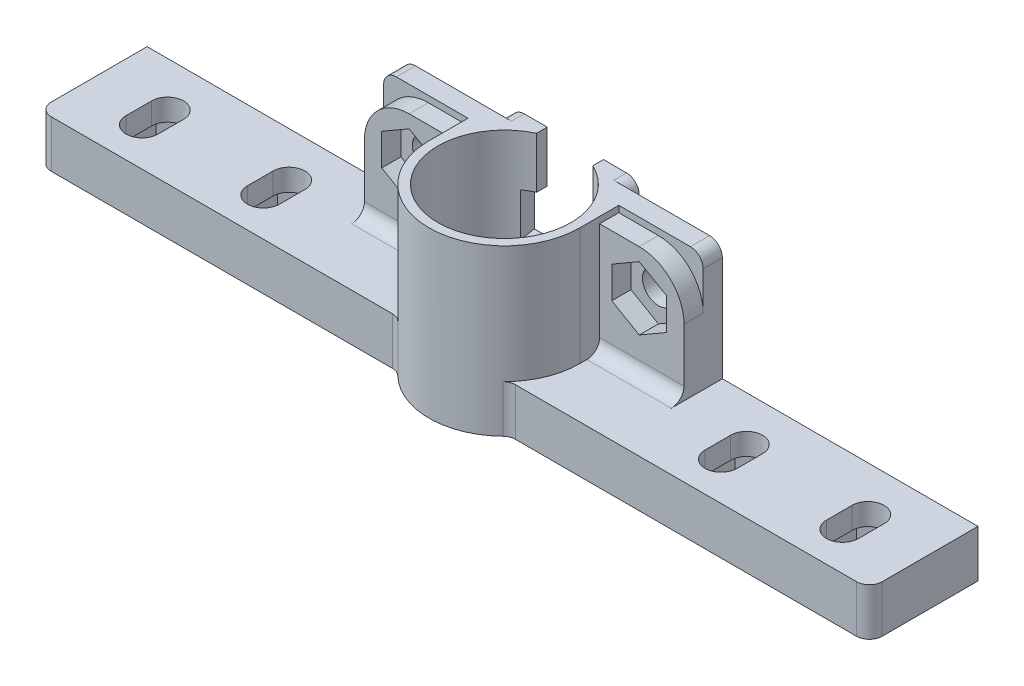
SolidWorks part; units mm, degrees
note: '?' marks a value the reader was unsure of.
ref_plane "Front Plane" through (0, 0, 0) normal (0, 0, 1) x (1, 0, 0)
ref_plane "Top Plane" through (0, 0, 0) normal (0, 1, 0) x (1, 0, 0)
ref_plane "Right Plane" through (0, 0, 0) normal (1, 0, 0) x (0, 0, -1)
sketch "Sketch1" plane through (0, 0, 0) normal (0, 1, 0) x (1, 0, 0)
  line L0 (-2.0019, 5.55) -> (2.0019, 5.55)
  line L1 (5, 4.55) -> (12.5, 4.55)
  line L2 (5.0505, 3.05) -> (12.5, 3.05)
  line L3 (12.5, 4.55) -> (12.5, 3.05)
  line L4 (0, 13.9078) -> (0, -10.692) construction
  line L5 (2.0019, 5.55) -> (5, 5.55)
  line L6 (5, 5.55) -> (5, 4.55)
  line L7 (-5.0505, 3.05) -> (-12.5, 3.05)
  line L8 (-12.5, 4.55) -> (-12.5, 3.05)
  line L9 (-5, 4.55) -> (-12.5, 4.55)
  line L10 (-5, 5.55) -> (-5, 4.55)
  line L11 (-2.0019, 5.55) -> (-5, 5.55)
  line L12 (-5.9, 0) -> (-5.9, 3.05)
  line L13 (5.9, 0) -> (5.9, 3.05)
  circle A0 centre (0, 0) radius 5.2
  circle A1 centre (0, 0) radius 5.9
  point P6 (0, 5.2)
  dimension "D1" = 10.4
  dimension "D2" = 0.7
  dimension "D3" = 0.35
  dimension "D4" = 1
  dimension "D5" = 1.5
  dimension "D6" = 25
  dimension "D7" = 10
extrude "Base shape" add sketch "Sketch1" along normal blind 11.4 contours A1 L9 L8 L7 | A1 L11 L10 | L4 L0 A1 A0 | L0 L4 A0 A1 | A1 L6 L5 | A1 L2 L3 L1
sketch "Sketch2" plane through (0, 0, 0) normal (0, -1, 0) x (1, 0, 0)
  line L9 (-5.9, -3.05) -> (-12.5, -3.05)
  line L10 (-12.5, -3.05) -> (-12.5, -4.55)
  line L11 (-12.5, -4.55) -> (-5, -4.55)
  line L12 (-5, -4.55) -> (-5, -5.55)
  line L13 (-5, -5.55) -> (5, -5.55)
  line L14 (5, -5.55) -> (5, -4.55)
  line L15 (5, -4.55) -> (12.5, -4.55)
  line L16 (12.5, -4.55) -> (12.5, -3.05)
  line L17 (12.5, -3.05) -> (5.9, -3.05)
  line L18 (-5.9, -3.05) -> (-12.5, -3.05)
  line L19 (-12.5, -3.05) -> (-12.5, -4.55)
  line L20 (-12.5, -4.55) -> (-5, -4.55)
  line L21 (-5, -4.55) -> (-5, -5.55)
  line L22 (-5, -5.55) -> (5, -5.55)
  line L23 (5, -5.55) -> (5, -4.55)
  line L24 (5, -4.55) -> (12.5, -4.55)
  line L25 (12.5, -4.55) -> (12.5, -3.05)
  line L26 (12.5, -3.05) -> (5.9, -3.05)
  line L29 (5.9, -3.05) -> (5.9, 0)
  line L30 (5.9, -3.05) -> (5.9, 0)
  line L31 (-5.9, 0) -> (-5.9, -3.05)
  line L32 (-5.9, 0) -> (-5.9, -3.05)
  arc A1 (5.9, 0) -> (-5.9, 0) centre (0, 0) ccw
  arc A2 (5.9, 0) -> (-5.9, 0) centre (0, 0) ccw
  dimension "D1" = 0
extrude "Bottom extrude" add sketch "Sketch2" along normal blind 1.5
sketch "Sketch3" plane through (0, 0, 0) normal (0, 1, 0) x (1, 0, 0)
  circle A0 centre (0, 0) radius 3
  dimension "D1" = 6
extrude "Pin cut" cut sketch "Sketch3" against normal up to next
sketch "Sketch5" plane through (0, 0, -4.55) normal (0, 0, -1) x (-1, 0, 0)
  line L0 (-9, 11.4) -> (-9, -1.5) construction
  line L1 (-5, 11.4) -> (-12.5, 11.4) construction
  line L2 (-5, -1.5) -> (-12.5, -1.5) construction
  line L3 (0, 18.7568) -> (0, -7.6861) construction
  circle A0 centre (-9, 7.4) radius 1.25
  circle A1 centre (9, 7.4) radius 1.25
  dimension "D2" = 2.5
  dimension "D1" = 18
  dimension "D3" = 4
extrude "M2 screw holes" cut sketch "Sketch5" against normal up to next
sketch "Sketch6" plane through (0, 0, -3.05) normal (0, 0, 1) x (1, 0, 0)
  line L0 (0, 17.5657) -> (0, -6.5546) construction
  line L1 (-5.9, 11.4) -> (-5.9, -1.5) construction
  line L2 (-5.9, 11.4) -> (-5.9, -1.5)
  line L3 (-12.5, 7.4) -> (-12.5, -1.5)
  line L4 (-5.9, -1.5) -> (-12.5, -1.5) construction
  line L5 (-12.5, -1.5) -> (-5.9, -1.5)
  line L6 (12.5, -1.5) -> (5.9, -1.5)
  line L7 (12.5, 7.4) -> (12.5, -1.5)
  line L8 (5.9, 11.4) -> (5.9, -1.5)
  line L9 (-9, 10.9) -> (-5.9, 10.9)
  line L10 (9, 10.9) -> (5.9, 10.9)
  line L11 (-12.5, 11.4) -> (-12.5, -1.5) construction
  line L12 (-9, 9.8826) -> (-11.15, 8.6413)
  line L13 (-11.15, 8.6413) -> (-11.15, 6.1587)
  line L14 (-11.15, 6.1587) -> (-9, 4.9174)
  line L15 (-9, 4.9174) -> (-6.85, 6.1587)
  line L16 (-6.85, 6.1587) -> (-6.85, 8.6413)
  line L17 (-6.85, 8.6413) -> (-9, 9.8826)
  line L18 (6.85, 8.6413) -> (9, 9.8826)
  line L19 (6.85, 6.1587) -> (6.85, 8.6413)
  line L20 (9, 4.9174) -> (6.85, 6.1587)
  line L21 (11.15, 6.1587) -> (9, 4.9174)
  line L22 (11.15, 8.6413) -> (11.15, 6.1587)
  line L23 (9, 9.8826) -> (11.15, 8.6413)
  circle A1 centre (-9, 7.4) radius 1.25 construction
  circle A2 centre (-9, 7.4) radius 1.25
  circle A4 centre (9, 7.4) radius 1.25
  circle A5 centre (-9, 7.4) radius 3.5
  circle A6 centre (9, 7.4) radius 3.5
  circle A7 centre (-9, 7.4) radius 2.15 construction
  line M5 (-12.5, -1.5) -> (-5.9, -1.5)
  line M11 (-12.5, 11.4) -> (-12.5, -1.5)
  line M12 (-5.9, -1.5) -> (-5.9, 11.4)
  dimension "D2" = 4.3
extrude "Extra thread extrudes" add sketch "Sketch6" along normal blind 1.5 contours L2 A5 L17 L16 L15 L14 L13 L12 | A5 M11 M5 M12 | A6 L8 L18 L23 L22 L21 L20 L19 | L7 A6 L8 L6 | L8 A6 L10 | A5 L9 M12
sketch "Sketch7" plane through (0, 0, 0) normal (0, 1, 0) x (1, 0, 0)
  circle A0 centre (0, 0) radius 4.05
  circle A1 centre (0, 0) radius 5.2 construction
  circle A3 centre (0, 0) radius 3 construction
  dimension "D2" = 1.05
extrude "Inner bearing free cut" cut sketch "Sketch7" against normal blind 0.5
ref_plane "Bumper plane" through (0, 5.7, 0) normal (0, 1, 0) x (1, 0, 0)
sketch "Sketch8" plane through (0, 5.7, 0) normal (0, 1, 0) x (1, 0, 0)
  line L0 (-2.1666, -0.382) -> (-3.2126, 5.55)
  line L1 (0, 15.952) -> (0, -10.9908) construction
  line L2 (2.1666, -0.382) -> (3.2126, 5.55)
  line L3 (-3.2126, 5.55) -> (3.2126, 5.55)
  line L4 (-5, 5.55) -> (5, 5.55) construction
  circle A0 centre (0, 0) radius 2.2
  dimension "D1" = 4.4
  dimension "D2" = 10
extrude "Bumper cut" cut sketch "Sketch8" against normal mid plane 3.4 contours L1 L3 L0 A0 | L3 L1 A0 L2 | A0 L1 | L1 A0
fillet "Milled hole fillets" radius 1 6 edges at (-12.5, 11.4, -3.8) (12.5, 11.4, -3.8) (-5, -1.5, -5.05) (-5, 11.4, -5.05) (5, -1.5, -5.05) (5, 11.4, -5.05)
sketch "Sketch9" plane through (0, 0, -5.55) normal (0, 0, -1) x (-1, 0, 0)
  line L0 (0, 13.5286) -> (0, -4.0503) construction
  line L1 (4, 11.4) -> (-4, 11.4) construction
  line L2 (-2.2, 7.4) -> (2.2, 7.4)
  line L3 (-2.2, 7.4) -> (-2.2, 11.4)
  line L4 (-2.2, 11.4) -> (2.2, 11.4)
  line L5 (2.2, 7.4) -> (2.2, 11.4)
  line L6 (-2.2, 7.4) -> (2.2, 11.4) construction
  line L7 (-2.2, 11.4) -> (2.2, 7.4) construction
  line L8 (-2.9848, 7.4) -> (2.9848, 7.4) construction
  point P1 (0, 9.4)
  dimension "D1" = 4.4
extrude "Bumper body top cut" cut sketch "Sketch9" against normal up to next
sketch "Sketch10" plane through (0, -1.5, 0) normal (0, -1, 0) x (1, 0, 0)
  line L0 (-12.5, 5.9) -> (0, 5.9)
  line L1 (-12.5, -4.55) -> (-32.5, -4.55)
  line L2 (-12.5, -4.55) -> (-12.5, 5.9)
  line L3 (-12.5, 5.9) -> (-32.5, 5.9)
  line L4 (-32.5, -4.55) -> (-32.5, 5.9)
  line L5 (0, 5.9) -> (32.5, 5.9)
  line L6 (-5.9, -1.55) -> (-12.5, -1.55)
  line L7 (-17.9, 5.9) -> (-17.9, -4.55) construction
  line L8 (-17.9, -1.05) -> (-17.9, 0.95) construction
  line L9 (-19.15, -1.05) -> (-19.15, 0.95)
  line L10 (-16.65, -1.05) -> (-16.65, 0.95)
  line L11 (-22.65, 5.9) -> (-22.65, -4.55) construction
  line L12 (-27.4, -1.05) -> (-27.4, 0.95) construction
  line L13 (-26.15, -1.05) -> (-26.15, 0.95)
  line L14 (-28.65, -1.05) -> (-28.65, 0.95)
  line L15 (0, 10.619) -> (0, -12.8113) construction
  line L16 (17.9, -1.05) -> (17.9, 0.95) construction
  line L17 (19.15, -1.05) -> (19.15, 0.95)
  line L18 (16.65, -1.05) -> (16.65, 0.95)
  line L19 (27.4, -1.05) -> (27.4, 0.95) construction
  line L20 (26.15, -1.05) -> (26.15, 0.95)
  line L21 (28.65, -1.05) -> (28.65, 0.95)
  line L25 (12.5, -4.55) -> (32.5, -4.55)
  line L26 (32.5, -4.55) -> (32.5, 5.9)
  line L28 (5.9, -1.55) -> (12.5, -1.55)
  line L30 (12.5, -1.55) -> (12.5, -4.55)
  line L31 (-32.5, -0.05) -> (-12.5, -0.05) construction
  line L32 (-32.5, 3.95) -> (32.5, 3.95)
  arc A0 (-19.15, -1.05) -> (-16.65, -1.05) centre (-17.9, -1.05) ccw
  arc A1 (-16.65, 0.95) -> (-19.15, 0.95) centre (-17.9, 0.95) ccw
  arc A2 (-26.15, -1.05) -> (-28.65, -1.05) centre (-27.4, -1.05) cw
  arc A3 (-28.65, 0.95) -> (-26.15, 0.95) centre (-27.4, 0.95) cw
  arc A4 (19.15, -1.05) -> (16.65, -1.05) centre (17.9, -1.05) cw
  arc A5 (16.65, 0.95) -> (19.15, 0.95) centre (17.9, 0.95) cw
  arc A6 (26.15, -1.05) -> (28.65, -1.05) centre (27.4, -1.05) ccw
  arc A7 (28.65, 0.95) -> (26.15, 0.95) centre (27.4, 0.95) ccw
  arc A9 (5.9, 0) -> (-5.9, 0) centre (0, 0) ccw construction
  point P13 (-17.9, -0.05)
  point P22 (-27.4, -0.05)
  point P32 (17.9, -0.05)
  point P39 (27.4, -0.05)
  dimension "D1" = 20
  dimension "D2" = 3
  dimension "D3" = 5.4
  dimension "D4" = 4.5
  dimension "D5" = 2.5
  dimension "D6" = 2
  dimension "D7" = 9.5
extrude "Bumper switch mount extrude" add sketch "Sketch10" against normal blind 3.7
fillet "Bumper switch mount fillets" radius 1 6 edges at (9.2, 2.2, -1.55) (-9.2, 2.2, -1.55) (4.3826, 0.35, 3.95) (-4.3826, 0.35, 3.95) (32.5, 0.35, 3.95) (-32.5, 0.35, 3.95)
sketch "Bumper mount axis sketch" plane through (0, 2.2, 0) normal (0, 1, 0) x (1, 0, 0)
  line L0 (-28.65, 0.05) -> (-26.15, 0.05) construction
  line L1 (-28.65, 1.05) -> (-28.65, -0.95) construction
  line L2 (-26.15, 1.05) -> (-26.15, -0.95) construction
  line L3 (-19.15, 0.05) -> (-16.65, 0.05) construction
  line L4 (-19.15, 1.05) -> (-19.15, -0.95) construction
  line L5 (-16.65, 1.05) -> (-16.65, -0.95) construction
  line L6 (16.65, 0.05) -> (19.15, 0.05) construction
  line L7 (16.65, 1.05) -> (16.65, -0.95) construction
  line L8 (19.15, 1.05) -> (19.15, -0.95) construction
  line L9 (26.15, 0.05) -> (28.65, 0.05) construction
  line L10 (26.15, 1.05) -> (26.15, -0.95) construction
  line L11 (28.65, 1.05) -> (28.65, -0.95) construction
  point P12 (-27.4, 0.05)
  point P13 (-17.9, 0.05)
  point P26 (17.9, 0.05)
  point P27 (27.4, 0.05)
sketch "Sketch12" plane through (0, -1.5, 0) normal (0, -1, 0) x (1, 0, 0)
  line L0 (-28.65, -0.05) -> (28.65, -0.05) construction
  line L1 (-27.4, 3.4326) -> (-29.55, 2.1913)
  line L2 (-29.55, 2.1913) -> (-29.55, -0.2913)
  line L3 (-29.55, -0.2913) -> (-27.4, -1.5326)
  line L4 (-27.4, -1.5326) -> (-25.25, -0.2913)
  line L5 (-25.25, -0.2913) -> (-25.25, 2.1913)
  line L6 (-25.25, 2.1913) -> (-27.4, 3.4326)
  line L7 (-28.65, -1.05) -> (-28.65, 0.95) construction
  line L8 (28.65, -1.05) -> (28.65, 0.95) construction
  line L9 (-25.25, 0.1913) -> (-25.25, -2.2913)
  line L10 (-25.25, -2.2913) -> (-27.4, -3.5326)
  line L11 (-27.4, -3.5326) -> (-29.55, -2.2913)
  line L12 (-29.55, -2.2913) -> (-29.55, 0.1913)
  line L13 (-17.9, -3.5326) -> (-20.05, -2.2913)
  line L14 (-17.9, 3.4326) -> (-20.05, 2.1913)
  line L15 (-20.05, 2.1913) -> (-20.05, -0.2913)
  line L16 (-20.05, -0.2913) -> (-17.9, -1.5326)
  line L17 (-17.9, -1.5326) -> (-15.75, -0.2913)
  line L18 (-15.75, -0.2913) -> (-15.75, 2.1913)
  line L19 (-15.75, 2.1913) -> (-17.9, 3.4326)
  line L20 (-15.75, -2.2913) -> (-17.9, -3.5326)
  line L21 (-15.75, 0.1913) -> (-15.75, -2.2913)
  line L24 (-20.05, -2.2913) -> (-20.05, 0.1913)
  line L25 (0, 11.4466) -> (0, -12.1599) construction
  line L26 (17.9, -3.5326) -> (20.05, -2.2913)
  line L27 (15.75, -2.2913) -> (17.9, -3.5326)
  line L28 (15.75, 0.1913) -> (15.75, -2.2913)
  line L29 (15.75, -0.2913) -> (15.75, 2.1913)
  line L30 (15.75, 2.1913) -> (17.9, 3.4326)
  line L31 (17.9, 3.4326) -> (20.05, 2.1913)
  line L32 (20.05, 2.1913) -> (20.05, -0.2913)
  line L33 (20.05, -2.2913) -> (20.05, 0.1913)
  line L34 (29.55, -2.2913) -> (29.55, 0.1913)
  line L35 (27.4, -3.5326) -> (29.55, -2.2913)
  line L36 (25.25, -2.2913) -> (27.4, -3.5326)
  line L37 (25.25, 0.1913) -> (25.25, -2.2913)
  line L38 (25.25, -0.2913) -> (25.25, 2.1913)
  line L39 (25.25, 2.1913) -> (27.4, 3.4326)
  line L40 (27.4, 3.4326) -> (29.55, 2.1913)
  line L41 (29.55, 2.1913) -> (29.55, -0.2913)
  line L42 (-29.55, 0.1913) -> (-29.55, -0.2913)
  circle A0 centre (-27.4, 0.95) radius 2.15 construction
  circle A1 centre (-17.9, 0.95) radius 2.15 construction
  arc M33 (-19.15, 0.95) -> (-16.65, 0.95) centre (-17.9, 0.95) cw
  line M34 (-16.65, 0.95) -> (-16.65, -1.05)
  arc M35 (-16.65, -1.05) -> (-19.15, -1.05) centre (-17.9, -1.05) cw
  line M36 (-19.15, -1.05) -> (-19.15, 0.95)
  line M37 (-28.65, -1.05) -> (-28.65, 0.95)
  arc M38 (-28.65, 0.95) -> (-26.15, 0.95) centre (-27.4, 0.95) cw
  line M39 (-26.15, 0.95) -> (-26.15, -1.05)
  arc M40 (-26.15, -1.05) -> (-28.65, -1.05) centre (-27.4, -1.05) cw
  arc M41 (26.15, 0.95) -> (28.65, 0.95) centre (27.4, 0.95) cw
  line M42 (28.65, 0.95) -> (28.65, -1.05)
  arc M43 (28.65, -1.05) -> (26.15, -1.05) centre (27.4, -1.05) cw
  line M44 (26.15, -1.05) -> (26.15, 0.95)
  line M45 (16.65, -1.05) -> (16.65, 0.95)
  arc M46 (16.65, 0.95) -> (19.15, 0.95) centre (17.9, 0.95) cw
  line M47 (19.15, 0.95) -> (19.15, -1.05)
  arc M48 (19.15, -1.05) -> (16.65, -1.05) centre (17.9, -1.05) cw
  dimension "D1" = 4.3
extrude "Bumper switch nut cuts" cut sketch "Sketch12" against normal blind 2 contours L5 L6 L1 L2 L3 L4 M40 M37 M38 M39 | L12 L11 L10 L9 L4 L3 | L24 L13 L20 L21 L17 L16 | L18 L19 L14 L15 L16 L17 M36 M33 M34 M35 | L26 L33 L32 L31 L30 L29 L28 L27 M48 M45 M46 M47 | L41 L40 L39 L38 L37 L36 L35 L34 M44 M41 M42 M43
ref_axis "Left outer" through (-27.4, 2.2, -0.05) along (0, 1, 0)?
ref_axis "Left inner" through (-17.9, 2.2, -0.05) along (0, 1, 0)?
ref_axis "Right inner" through (17.9, 2.2, -0.05) along (0, 1, 0)?
ref_axis "Right outer" through (27.4, 2.2, -0.05) along (0, 1, 0)?
